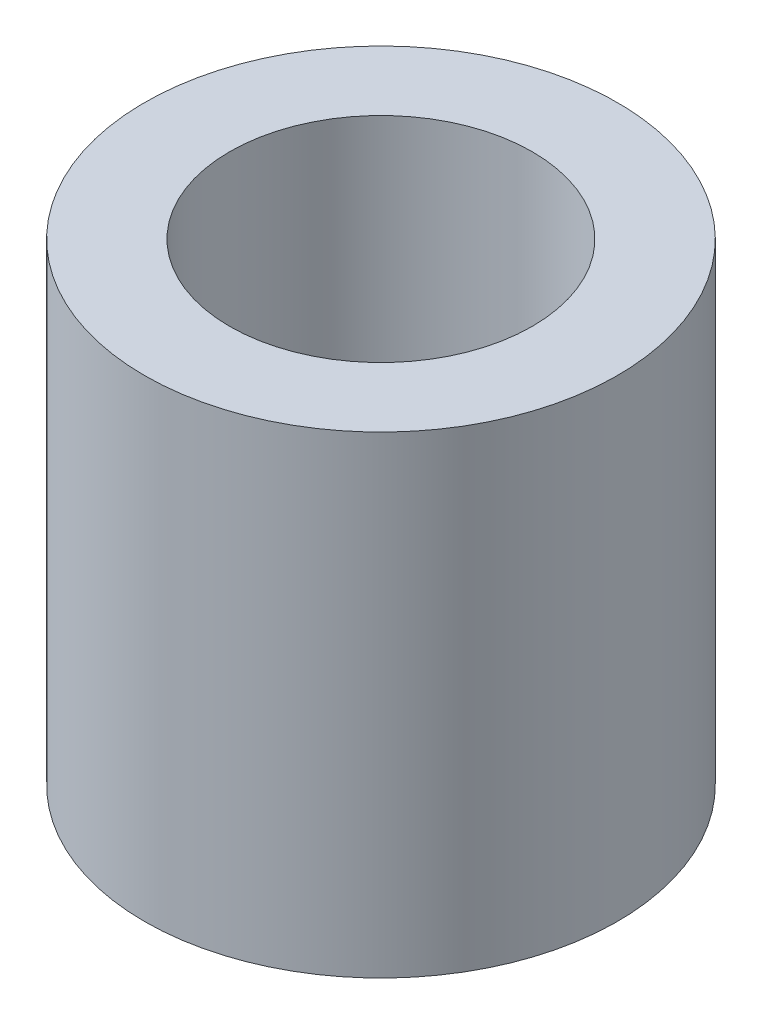
SolidWorks part; units mm, degrees
ref_plane "Front Plane" through (0, 0, 0) normal (0, 0, 1) x (1, 0, 0)
ref_plane "Top Plane" through (0, 0, 0) normal (0, 1, 0) x (1, 0, 0)
ref_plane "Right Plane" through (0, 0, 0) normal (1, 0, 0) x (0, 0, -1)
sketch "Sketch1" plane through (0, 0, 0) normal (0, 1, 0) x (1, 0, 0)
  circle A0 centre (0, 0) radius 2.5
  circle A1 centre (0, 0) radius 1.6
  dimension "D1" = 5
  dimension "D2" = 3.2
extrude "Boss-Extrude1" add sketch "Sketch1" along normal blind 2.5 and the other way blind 2.5
